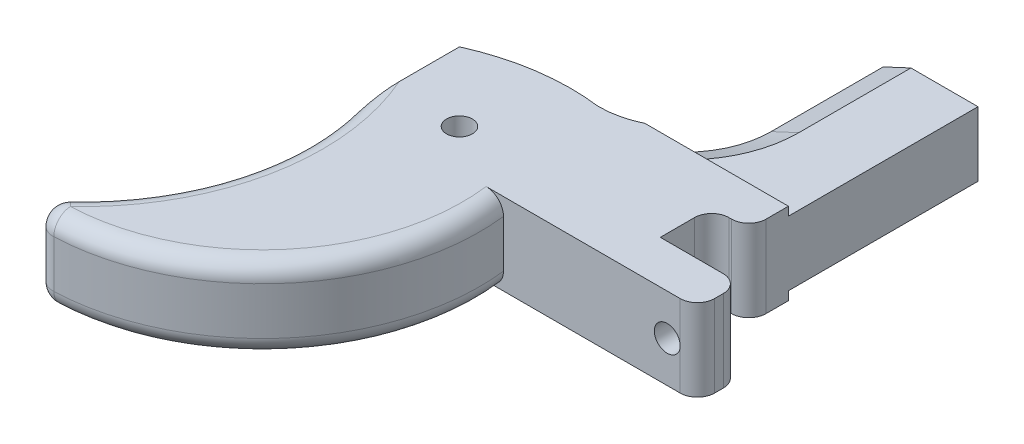
SolidWorks part; units mm, degrees
ref_plane "Alzado" through (0, 0, 0) normal (0, 0, 1) x (1, 0, 0)
ref_plane "Planta" through (0, 0, 0) normal (0, 1, 0) x (1, 0, 0)
ref_plane "Vista lateral" through (0, 0, 0) normal (1, 0, 0) x (0, 0, -1)
sketch "Croquis1" plane through (0, 0, 0) normal (0, 1, 0) x (1, 0, 0)
  line L0 (0, 0) -> (0, 14)
  line L4 (0, 14) -> (17.6008, 14)
  line L5 (17.6008, 14) -> (17.6008, 1.5094)
  arc A3 (0, 0) -> (-11.9221, -26.243) centre (-25.5911, -4.2037) cw
  arc A4 (-11.9221, -26.243) -> (17.6008, 1.5094) centre (-7.4564, -1.4143) ccw
  circle A6 centre (8, 6) radius 1.5
  point P1 (0, 0)
  point P5 (0, 0)
  dimension "D5" = 25.2272
  dimension "D6" = 8
  dimension "D2" = 25.934
  dimension "D15" = 3
  dimension "D7" = 12.4906
  dimension "D3" = 14
  dimension "D4" = 7.5893
  dimension "D9" = 1.4143
  dimension "D10" = 25.5911
  dimension "D17" = 6
extrude "Saliente-Extruir1" add sketch "Croquis1" along normal blind 9.5
sketch "Croquis2" plane through (0, 9.5, 0) normal (0, 1, 0) x (1, 0, 0)
  line L0 (17.6008, 1.5094) -> (20.1008, 1.5094)
  line L1 (20.1008, 1.5094) -> (20.1008, 14.5094)
  line L2 (0, 14) -> (17.6008, 14)
  line L3 (17.6008, 14) -> (17.6008, 1.5094)
  arc A1 (0, 14) -> (20.1008, 14.5094) centre (10.6579, -9.7152) cw
  dimension "D2" = 13
  dimension "D3" = 26
  dimension "D1" = 2.5
extrude "Saliente-Extruir2" add sketch "Croquis2" against normal blind 9.5
fillet "Redondeo1" radius 7 1 edges at (20.1008, 4.75, -14.5094)
sketch "Croquis3" plane through (0, 9.5, 0) normal (0, 1, 0) x (1, 0, 0)
  line L0 (20.1008, 1.5094) -> (40.1008, 1.5094)
  line L1 (40.1008, 1.5094) -> (40.1008, 6.5094)
  line L2 (40.1008, 6.5094) -> (20.1008, 6.5094)
  line L3 (20.1008, 1.5094) -> (20.1008, 9.1271) construction
  line L4 (20.1008, 6.5094) -> (20.1008, 1.5094)
  dimension "D1" = 5
  dimension "D2" = 20
extrude "Saliente-Extruir3" add sketch "Croquis3" against normal blind 9.5
fillet "Redondeo2" radius 2 2 edges at (40.1008, 4.75, -1.5094) (40.1008, 4.75, -6.5094)
sketch "Croquis5" plane through (0, 9.5, 0) normal (0, 1, 0) x (1, 0, 0)
  line L0 (35.1008, 14.4733) -> (35.1008, 39.069)
  line L1 (38.1008, 6.5094) -> (20.1008, 6.5094) construction
  line L2 (35.1008, 39.069) -> (24.1008, 39.069)
  line L4 (33.1008, 12.4733) -> (32.7957, 12.4733)
  line L6 (30.7957, 6.5094) -> (20.1008, 6.5094)
  line L7 (24.1008, 26.069) -> (24.1008, 39.069)
  line L8 (14.0009, 16.069) -> (14.1008, 16.069)
  line L9 (20.1008, 6.5094) -> (20.1008, 9.1271) construction
  line L10 (20.1008, 6.5094) -> (20.1008, 9.1271)
  line L11 (30.7957, 10.4733) -> (30.7957, 6.5094)
  arc A0 (33.1008, 12.4733) -> (35.1008, 14.4733) centre (33.1008, 14.4733) ccw
  arc A2 (24.1008, 26.069) -> (14.1008, 16.069) centre (14.1008, 26.069) cw
  arc A3 (20.1008, 9.1271) -> (14.0009, 16.069) centre (13.1008, 9.1271) ccw construction
  arc A4 (20.1008, 9.1271) -> (14.0009, 16.069) centre (13.1008, 9.1271) ccw
  arc A5 (30.7957, 10.4733) -> (32.7957, 12.4733) centre (32.7957, 10.4733) cw
  dimension "D4" = 10
  dimension "D1" = 2
  dimension "D2" = 2
  dimension "D7" = 10.6948
  dimension "D3" = 11
  dimension "D5" = 24.5957
  dimension "D6" = 13
  dimension "D8" = 15
extrude "Saliente-Extruir4" add sketch "Croquis5" against normal blind 9.5
fillet "Redondeo3" radius 2 5 edges at (9.8223, 0, 19.7952) (9.8223, 9.5, 19.7952) (-1.9794, 0, 14.9304) (-1.9794, 9.5, 14.9304) (-11.9221, 4.75, 26.243)
sketch "Croquis6" plane through (0, 0, 0) normal (1, 0, 0) x (0, 0, -1)
  line L0 (39.069, 0) -> (39.069, 1)
  line L1 (39.069, 0) -> (39.069, 9.5) construction
  line L2 (39.069, 1) -> (17.069, 1)
  line L3 (17.069, 1) -> (17.069, 0)
  line L4 (16.069, 0) -> (26.069, 0) construction
  line L5 (17.069, 0) -> (39.069, 0)
  line L6 (39.069, 8.5) -> (17.069, 8.5)
  line L7 (17.069, 8.5) -> (17.069, 9.5)
  line L8 (26.069, 9.5) -> (16.069, 9.5) construction
  line L9 (17.069, 9.5) -> (39.069, 9.5)
  line L10 (39.069, 9.5) -> (39.069, 8.5)
  dimension "D1" = 1
  dimension "D2" = 1
  dimension "D3" = 22
  dimension "D4" = 22
extrude "Cortar-Extruir2" cut sketch "Croquis6" along normal blind 52
chamfer "Chaflán1" distance 1.5 angle 65 4 edges at (24.1008, 8.5, -32.569) (22.574, 8.5, -20.7581) (24.1008, 1, -32.569) (22.574, 1, -20.7581) first distance on face at (24.1008, 4.75, -32.569) first distance on face at (19.1178, 4.75, -18.8046)
sketch "Croquis7" plane through (0, 0, -1.5094) normal (0, 0, 1) x (1, 0, 0)
  line L0 (38.1008, 4.75) -> (17.6008, 4.75) construction
  line L1 (38.1008, 0) -> (38.1008, 9.5) construction
  line L2 (17.6008, 7.5) -> (17.6008, 2) construction
  circle A0 centre (36.6008, 4.75) radius 1.5
  dimension "D1" = 3
  dimension "D2" = 1.5
extrude "Cortar-Extruir3" cut sketch "Croquis7" against normal blind 52
